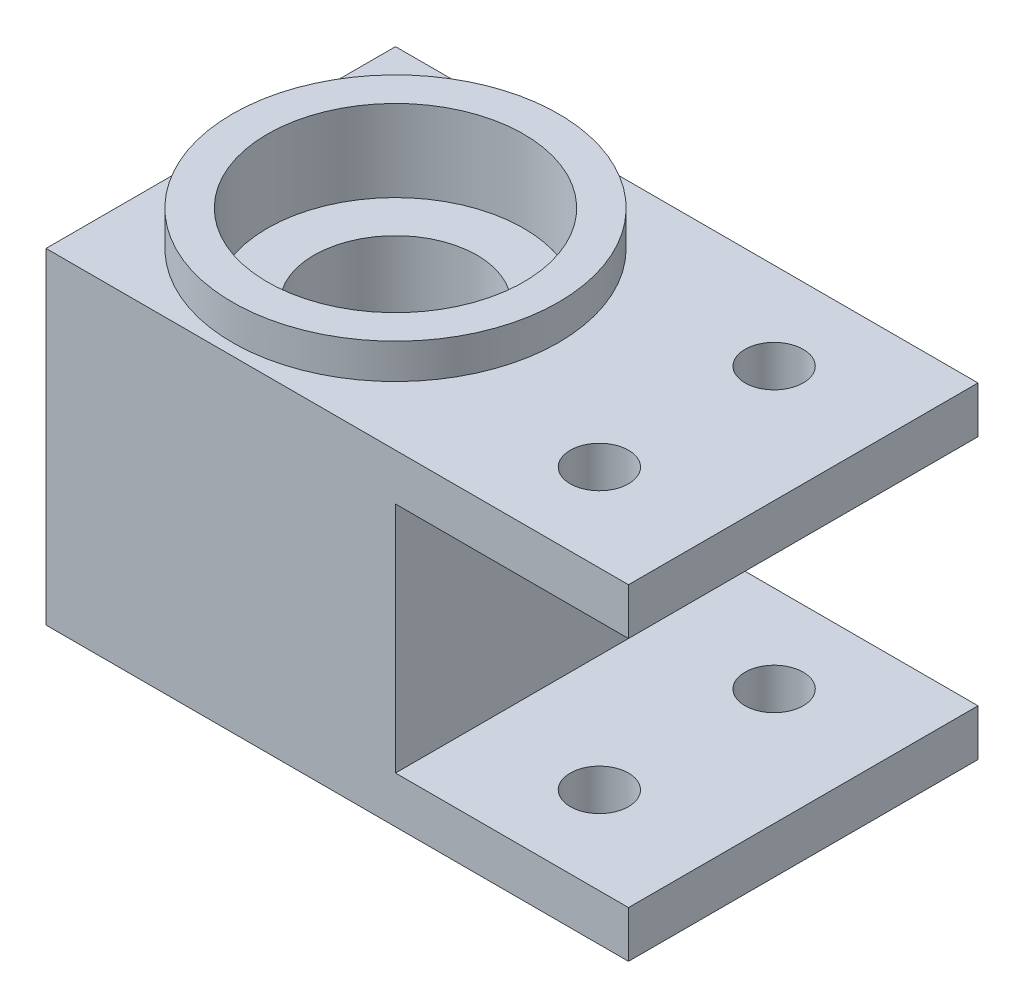
SolidWorks part; units mm, degrees
ref_plane "Front" through (0, 0, 0) normal (0, 0, 1) x (1, 0, 0)
ref_plane "Top" through (0, 0, 0) normal (0, 1, 0) x (1, 0, 0)
ref_plane "Right" through (0, 0, 0) normal (1, 0, 0) x (0, 0, -1)
sketch "Sketch1" plane through (0, 0, 0) normal (0, 0, 1) x (1, 0, 0)
  line L0 (10, 10) -> (10, 14)
  line L1 (-10, -10) -> (10, -10)
  line L2 (-10, -10) -> (-10, 10)
  line L3 (-10, 10) -> (10, 10)
  line L4 (10, -10) -> (10, 10) construction
  line L5 (-10, -10) -> (10, 10) construction
  line L6 (-10, 10) -> (10, -10) construction
  line L7 (10, 14) -> (-40, 14)
  line L8 (-40, 14) -> (-40, -14)
  line L9 (-40, -14) -> (10, -14)
  line L10 (10, -14) -> (10, -10)
  point P0 (0, 0)
  dimension "D1" = 20
  dimension "D2" = 4
  dimension "D3" = 50
  dimension "D4" = 28
extrude "Boss-Extrude1" add sketch "Sketch1" along normal blind 30
sketch "Sketch2" plane through (0, 14, 0) normal (0, 1, 0) x (1, 0, 0)
  line L0 (-40, -15) -> (-25, -15) construction
  line L2 (-40, -30) -> (-40, 0) construction
  circle A1 centre (-25, -15) radius 7
  dimension "D1" = 15
  dimension "D2" = 14
extrude "Cut-Extrude1" cut sketch "Sketch2" against normal through all
sketch "Sketch3" plane through (0, 14, 0) normal (0, 1, 0) x (1, 0, 0)
  circle A0 centre (-25, -15) radius 11
  dimension "D1" = 22
extrude "Cut-Extrude2" cut sketch "Sketch3" against normal blind 4
sketch "Sketch4" plane through (0, -14, 0) normal (0, -1, 0) x (1, 0, 0)
  circle A0 centre (-25, 15) radius 11 construction
  circle A1 centre (-25, 15) radius 11
extrude "Cut-Extrude3" cut sketch "Sketch4" against normal blind 7
sketch "Sketch5" plane through (0, 14, 0) normal (0, 1, 0) x (1, 0, 0)
  line L0 (10, 0) -> (-40, 0) construction
  line L1 (10, -30) -> (-40, -30) construction
  circle A0 centre (0, -7.5) radius 2.5
  circle A1 centre (0, -22.5) radius 2.5
  dimension "D1" = 5
  dimension "D2" = 5
  dimension "D3" = 7.5
  dimension "D4" = 7.5
extrude "Cut-Extrude4" cut sketch "Sketch5" against normal through all contours A1 | A0 region at (0, 14, 22.5)
sketch "Sketch6" plane through (0, 14, 0) normal (0, 1, 0) x (1, 0, 0)
  circle A0 centre (-25, -15) radius 11 construction
  circle A1 centre (-25, -15) radius 11
  circle A2 centre (-25, -15) radius 14
  dimension "D1" = 3
extrude "Boss-Extrude2" add sketch "Sketch6" along normal blind 3
